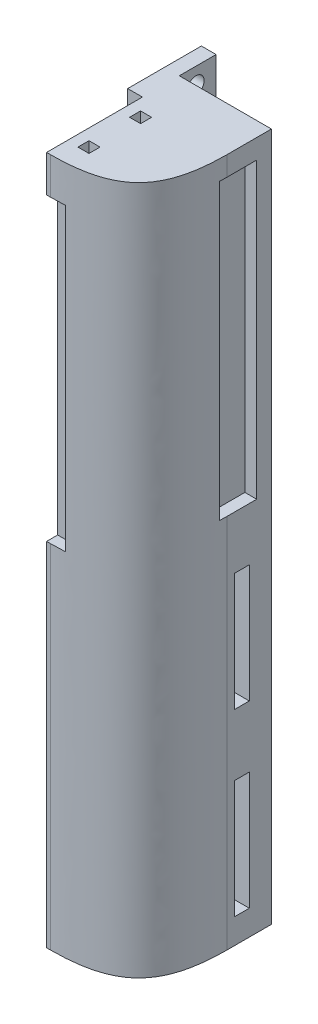
SolidWorks part; units mm, degrees
ref_plane "Front Plane" through (0, 0, 0) normal (0, 0, 1) x (1, 0, 0)
ref_plane "Top Plane" through (0, 0, 0) normal (0, 1, 0) x (1, 0, 0)
ref_plane "Right Plane" through (0, 0, 0) normal (1, 0, 0) x (0, 0, -1)
sketch "Sketch1" plane through (0, 0, 0) normal (0, 1, 0) x (1, 0, 0)
  line L1 (0, 0) -> (25, 0)
  line L2 (0, 0) -> (0, 36)
  line L3 (0, 36) -> (25, 36)
  line L4 (25, 0) -> (25, 36)
  dimension "D1" = 25
  dimension "D2" = 36
extrude "Boss-Extrude1" add sketch "Sketch1" along normal blind 186.9
fillet "Fillet1" radius 24 1 edges at (25, 93.45, 0) conic rho 0.55
ref_plane "Plane1" through (0, 0, 0) normal (0, 0, -1) x (-1, 0, 0)
sketch "Sketch2" plane through (0, 0, 0) normal (0, 0, -1) x (-1, 0, 0)
  line L1 (0, 176.9) -> (-5, 176.9)
  line L2 (0, 176.9) -> (0, 95.5)
  line L3 (0, 95.5) -> (-5, 95.5)
  line L4 (-5, 176.9) -> (-5, 95.5)
  line L5 (-1, 186.9) -> (-25, 186.9) construction
  dimension "D1" = 10
  dimension "D2" = 81.4
  dimension "D3" = 5
extrude "Cut-Extrude1" cut sketch "Sketch2" along normal blind 3
sketch "Sketch6" plane through (0, 0, -36) normal (0, 0, -1) x (-1, 0, 0)
  line L0 (0, 186.9) -> (0, 0) construction
  line L1 (0, 186.9) -> (4, 186.9)
  line L2 (0, 186.9) -> (0, 176.9)
  line L3 (0, 176.9) -> (4, 176.9)
  line L4 (4, 186.9) -> (4, 176.9)
  line L5 (0, 66.9) -> (4, 66.9)
  line L6 (0, 66.9) -> (0, 76.9)
  line L7 (0, 76.9) -> (4, 76.9)
  line L8 (4, 66.9) -> (4, 76.9)
  line L9 (-25, 186.9) -> (0, 186.9) construction
  dimension "D1" = 10
  dimension "D2" = 4
  dimension "D3" = 4
  dimension "D4" = 10
  dimension "D5" = 120
extrude "Boss-Extrude3" add sketch "Sketch6" against normal blind 10 and the other way blind 10
sketch "Sketch7" plane through (-4, 0, 0) normal (-1, 0, 0) x (0, 0, 1)
  line L0 (-36, 176.9) -> (-36, 76.9) construction
  line L1 (-46, 186.9) -> (-26, 186.9) construction
  line L2 (-46, 66.9) -> (-26, 66.9) construction
  line L3 (-36, 66.9) -> (-36, 0) construction
  circle A0 centre (-40.5, 182.4) radius 2.25
  circle A1 centre (-40.5, 71.4) radius 2.25
  dimension "D3" = 4.5
  dimension "D6" = 4.5
  dimension "D1" = 4.5
  dimension "D2" = 4.5
  dimension "D4" = 4.5
  dimension "D5" = 4.5
extrude "Cut-Extrude2" cut sketch "Sketch7" against normal up to next
chamfer "Chamfer1" distance 4 angle 45 1 edges at (0, 71.9, -26)
sketch "Sketch8" plane through (0, 0, 0) normal (-1, 0, 0) x (0, 0, 1)
  line L0 (-26, 186.9) -> (0, 186.9) construction
  line L1 (-10, 182.9) -> (-4, 182.9)
  line L2 (-10, 182.9) -> (-10, 178.9)
  line L3 (-10, 178.9) -> (-4, 178.9)
  line L4 (-4, 182.9) -> (-4, 178.9)
  line L5 (0, 13.75) -> (0, -13.75) construction
  line L7 (-24, 182.9) -> (-18, 182.9)
  line L8 (-24, 182.9) -> (-24, 178.9)
  line L9 (-24, 178.9) -> (-18, 178.9)
  line L10 (-18, 182.9) -> (-18, 178.9)
  dimension "D1" = 4
  dimension "D2" = 6
  dimension "D3" = 4
  dimension "D4" = 4
  dimension "D5" = 8
  dimension "D6" = 6
  dimension "D7" = 4
extrude "Cut-Extrude3" cut sketch "Sketch8" against normal blind 9
sketch "Sketch9" plane through (0, 186.9, 0) normal (0, 1, 0) x (1, 0, 0)
  line L0 (0, 0) -> (1, 0) construction
  line L1 (3, 5.5) -> (6, 5.5)
  line L2 (3, 5.5) -> (3, 8.5)
  line L3 (3, 8.5) -> (6, 8.5)
  line L4 (6, 5.5) -> (6, 8.5)
  line L5 (0, 26) -> (0, 0) construction
  line L7 (3, 19.5) -> (6, 19.5)
  line L8 (3, 19.5) -> (3, 22.5)
  line L9 (3, 22.5) -> (6, 22.5)
  line L10 (6, 19.5) -> (6, 22.5)
  dimension "D1" = 5.5
  dimension "D2" = 3
  dimension "D3" = 3
  dimension "D4" = 3
  dimension "D5" = 11
  dimension "D6" = 3
  dimension "D7" = 3
  dimension "D8" = 3
extrude "Cut-Extrude4" cut sketch "Sketch9" against normal blind 10
sketch "Sketch10" plane through (0, 0, 0) normal (0, -1, 0) x (1, 0, 0)
  line L0 (0, -36) -> (0, 0) construction
  line L1 (3, -5) -> (7, -5)
  line L2 (3, -5) -> (3, -33)
  line L3 (3, -33) -> (7, -33)
  line L4 (7, -5) -> (7, -29)
  line L5 (0, 0) -> (1, 0) construction
  line L6 (25, -36) -> (0, -36) construction
  line L7 (25, -24) -> (25, -36) construction
  line L8 (7, -33) -> (21, -33)
  line L10 (7, -29) -> (21, -29)
  line L11 (21, -33) -> (21, -29)
  dimension "D1" = 3
  dimension "D2" = 5
  dimension "D3" = 4
  dimension "D4" = 3
  dimension "D5" = 4
  dimension "D6" = 4
extrude "Boss-Extrude4" add sketch "Sketch10" along normal blind 4
sketch "Sketch11" plane through (0, 0, 0) normal (0, -1, 0) x (1, 0, 0)
  line L0 (21, -29) -> (7, -29) construction
  line L1 (7, -29) -> (7, -5) construction
  circle A0 centre (14, -22) radius 2
  dimension "D1" = 4
  dimension "D2" = 7
  dimension "D3" = 7
sketch "Sketch14" plane through (0, 0, 0) normal (0, 1, 0) x (-1, 0, 0)
  line L3 (0, -26) -> (0, 0) construction
  line L4 (-13.75, 0) -> (13.75, 0) construction
  circle A1 centre (-14, -11) radius 1.5
  dimension "D1" = 11
  dimension "D2" = 14
  dimension "D6" = 3
extrude "Cut-Extrude5" cut sketch "Sketch11" against normal blind 5
extrude "Cut-Extrude6" cut sketch "Sketch14" along normal blind 4
sketch "Sketch15" plane through (25, 0, 0) normal (1, 0, 0) x (0, 0, -1)
  line L0 (24, 186.9) -> (24, 0) construction
  line L1 (26, 87.5) -> (30, 87.5)
  line L2 (26, 87.5) -> (26, 55.5)
  line L3 (26, 55.5) -> (30, 55.5)
  line L4 (30, 87.5) -> (30, 55.5)
  line L6 (29, -4) -> (5, -4) construction
  line L7 (26, 38.8) -> (30, 38.8)
  line L8 (26, 38.8) -> (26, 6.8)
  line L9 (26, 6.8) -> (30, 6.8)
  line L10 (30, 38.8) -> (30, 6.8)
  dimension "D1" = 2
  dimension "D2" = 4
  dimension "D3" = 10.8
  dimension "D4" = 32
  dimension "D5" = 2
  dimension "D6" = 4
  dimension "D7" = 32
  dimension "D8" = 16.7
extrude "Cut-Extrude7" cut sketch "Sketch15" against normal blind 4
sketch "Sketch16" plane through (25, 0, 0) normal (1, 0, 0) x (0, 0, -1)
  line L0 (36, 186.9) -> (36, 0) construction
  line L1 (32, 181.6) -> (22, 181.6)
  line L2 (32, 181.6) -> (32, 101.9)
  line L3 (32, 101.9) -> (22, 101.9)
  line L4 (22, 181.6) -> (22, 101.9)
  line L5 (24, 186.9) -> (36, 186.9) construction
  dimension "D1" = 4
  dimension "D2" = 5.3
  dimension "D3" = 10
  dimension "D4" = 79.7
extrude "Cut-Extrude8" cut sketch "Sketch16" against normal blind 3.2
